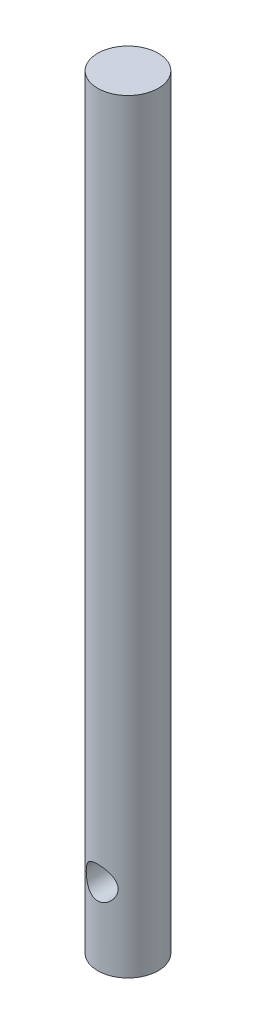
SolidWorks part; units mm, degrees
material "Plain Carbon Steel"
ref_plane "Front Plane" through (0, 0, 0) normal (0, 0, 1) x (1, 0, 0)
ref_plane "Top Plane" through (0, 0, 0) normal (0, 1, 0) x (1, 0, 0)
ref_plane "Right Plane" through (0, 0, 0) normal (1, 0, 0) x (0, 0, -1)
sketch "Sketch1" plane through (0, 0, 0) normal (0, 1, 0) x (1, 0, 0)
  circle A0 centre (0, 0) radius 4.7625
  dimension "D1" = 9.525
extrude "Boss-Extrude1" add sketch "Sketch1" along normal blind 120
sketch "Sketch2" plane through (0, 0, 0) normal (0, 0, 1) x (1, 0, 0)
  circle A0 centre (0, 12) radius 2.5
  dimension "D2" = 5
  dimension "D1" = 12
extrude "Cut-Extrude1" cut sketch "Sketch2" against normal mid plane 30
